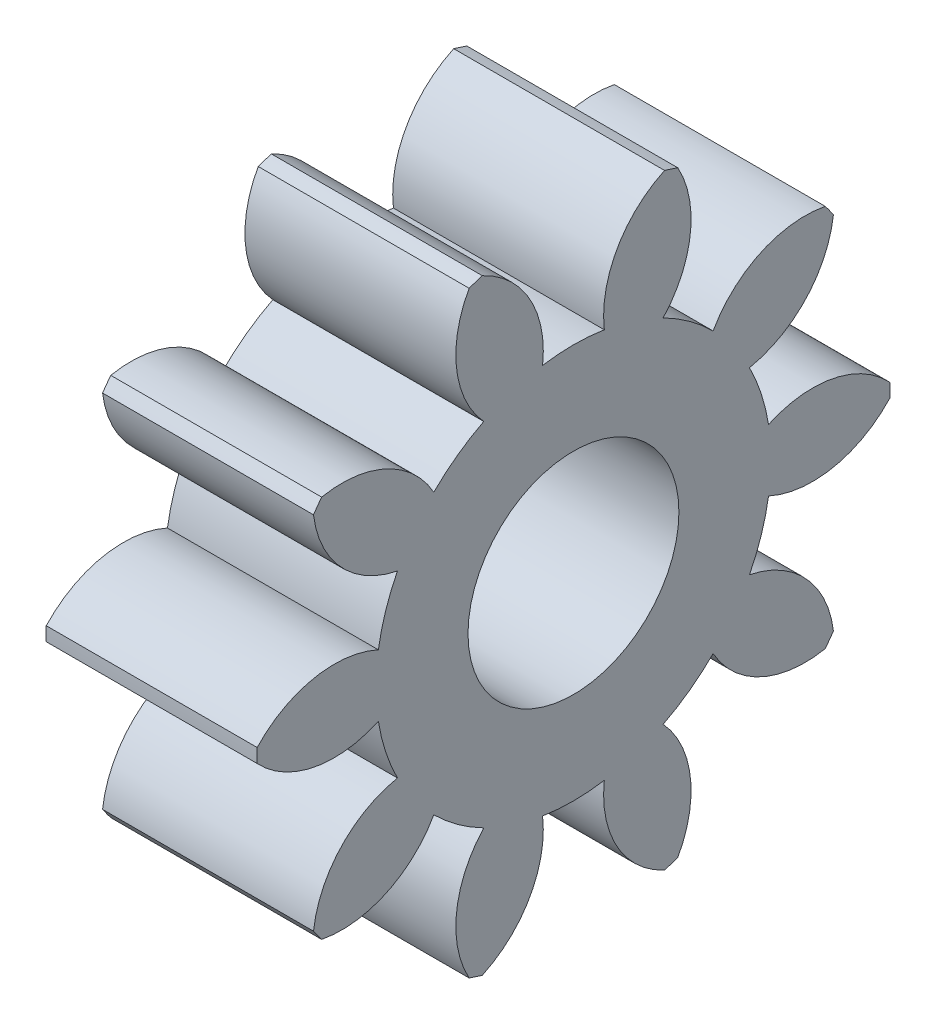
SolidWorks part; units mm, degrees
ref_plane "Plane1" through (0, 0, 0) normal (0, 0, 1) x (1, 0, 0)
ref_plane "Plane2" through (0, 0, 0) normal (0, 1, 0) x (1, 0, 0)
ref_plane "Plane3" through (0, 0, 0) normal (1, 0, 0) x (0, 0, -1)
sketch "HoldingSke" plane through (0, 0, 0) normal (0, 1, 0) x (1, 0, 0)
  line L0 (0, 0) -> (3.9392, -0.6946)
  line L1 (-15, 0) -> (100, 0) construction
  line L2 (0, 0) -> (-2.1039, 2.3779)
  line L3 (0, 0) -> (-11.863, 4.5341)
  line L4 (0, 0) -> (8.5048, 1.4996)
  line L5 (0, 0) -> (-46.8476, -17.4728)
  line L6 (0, 0) -> (-0.829, -0.5593)
  line L7 (-2.1039, 2.3779) -> (8.6586, 51.2059)
  line L8 (-76.2, 54.61) -> (-76.1, 54.61)
  line L9 (-71.009, 38.7566) -> (-53.1078, 45.2721)
  line L10 (-76.2, 71.12) -> (104.1128, 71.12)
  line L11 (0, 0) -> (-1, 0)
  line L12 (-76.2, 101.6) -> (-76.192, 101.6)
  line L13 (24.9733, 27.94) -> (52.9518, 28.4284)
  line L14 (24.9733, 27.94) -> (24.9743, 27.94)
  line L15 (24.9733, 27.94) -> (100.4006, 29.5858)
  line L16 (-63.627, -0.25) -> (-12.827, -0.25)
  circle A0 centre (0, 0) radius 0.5
  circle A1 centre (0, 0) radius 0.9365
  circle A2 centre (0, 0) radius 37.5
  circle A3 centre (0, 0) radius 0.5
  dimension "Num_teeth" = 10
  dimension "Pitch_radius" = 180.3128
  dimension "Width" = 1
  dimension "Thickness" = 1
sketch "BasProSke" plane through (0, 0, 0) normal (0, 1, 0) x (1, 0, 0)
  line L0 (-10, 0) -> (60, 0) construction
  line L1 (0, 0) -> (0, 1.5)
  line L2 (0, 0) -> (1, 0)
  line L3 (1, 0) -> (1, 1.5)
  line L4 (1, 1.5) -> (0, 1.5)
  dimension "Thickness" = 1
revolve "Base-Revolve" add sketch "BasProSke" angle 360 about L0
sketch "TooCutSke" plane through (0, 0, 0) normal (1, 0, 0) x (0, 0, -1)
  line L1 (0, 0) -> (0, 107) construction
  line L2 (0, 0) -> (-0.2095, 1.2323) construction
  line L3 (0, 0) -> (-0.7644, 2.3524) construction
  line L4 (-0.2095, 1.2323) -> (-0.3822, 1.1762) construction
  arc A0 (0.1463, 0.925) -> (-0.1463, 0.925) centre (0, 0) ccw
  arc A1 (0.4686, 1.4516) -> (-0.4686, 1.4516) centre (0, 0) ccw
  circle A2 centre (0, 0) radius 1.25 construction
  circle A3 centre (0, 0) radius 1.1746 construction
  arc A4 (-0.1463, 0.925) -> (-0.4686, 1.4516) centre (-0.6429, 0.983) ccw
  arc A5 (0.4686, 1.4516) -> (0.1463, 0.925) centre (0.6429, 0.983) ccw
extrude "ToothCut" cut sketch "TooCutSke" along normal through all
fillet "Breaks" [suppressed] radius 0.005 tangent propagation no
fillet "RootFillets" [suppressed] radius 0.0635
pattern_circular "TeethCuts" count 10 every 36 about axis through (-10, 0, 0) along (1, 0, 0) of "ToothCut", "RootFillets", "Breaks"
sketch "HubNeaOneSke" plane through (0, 0, 0) normal (-1, 0, 0) x (0, 0, 1)
  circle A0 centre (0, 0) radius 0.9365
extrude "HubNearOne" [suppressed] add sketch "HubNeaOneSke" along normal blind 49.0001
sketch "HubNeaBotSke" plane through (0, 0, 0) normal (-1, 0, 0) x (0, 0, 1)
  circle A0 centre (0, 0) radius 0.9365
extrude "HubNearBoth" [suppressed] add sketch "HubNeaBotSke" along normal blind 24.5
ref_plane "FarPln" through (1, 0, 0) normal (1, 0, 0) x (0, 0, -1)
sketch "HubFarSke" plane through (1, 0, 0) normal (1, 0, 0) x (0, 0, -1)
  circle A0 centre (0, 0) radius 0.9365
extrude "HubFar" [suppressed] add sketch "HubFarSke" along normal blind 24.5
sketch "BorSke" plane through (0, 0, 0) normal (1, 0, 0) x (0, 0, -1)
  circle A0 centre (0, 0) radius 0.5
  dimension "Diameter" = 1
extrude "Bore" cut sketch "BorSke" along normal mid plane 100.0001
sketch "KeySke" plane through (0, 0, 0) normal (1, 0, 0) x (0, 0, -1)
  line L0 (-0.05, 0) -> (-0.05, 0.6)
  line L1 (-0.05, 0.6) -> (0.05, 0.6)
  line L2 (0.05, 0.6) -> (0.05, 0)
  line L3 (0, 0) -> (0, 34) construction
  line L4 (-0.05, 0) -> (0.05, 0)
extrude "Keyway" [suppressed] cut sketch "KeySke" along normal mid plane 100.0001
pattern_circular "Keyway2" [suppressed] count 2 every 90 about axis through (-10, 0, 0) along (1, 0, 0) reverse direction yes
equation "' \"Module@HoldingSke\" = 6.35"
equation "' \"Num_teeth@HoldingSke\" = 12"
equation "' \"Ap@HoldingSke\" =  20"
equation "' \"Ap@HoldingSke\" = 20"
equation "' \"Width@HoldingSke\" = 0.5 * 25.4"
equation "' \"Hub_dia@HoldingSke\"= 1 * 25.4"
equation "' \"Hub_dia@HoldingSke\" = 1 * 25.4"
equation "' \"Overall_len@HoldingSke\" = 1.0 * 25.4"
equation "' \"Bore@HoldingSke\" = 0.75 * 25.4"
equation "' \"T_dim@HoldingSke\" = 0.1 * 25.4"
equation "' \"Width@KeySke\" = 0.25 * 25.4"
equation "' \"Show_teeth@HoldingSke\" = 13"
equation "' \"Backlash@HoldingSke\" = 0.009 * 25.4"
equation "' \"Addendum_fac@HoldingSke\" = 1.0"
equation "' \"Dedendum_fac@HoldingSke\" = 1.25"
equation "' \"Dedendum_add@HoldingSke\" = 0.00005 * 25.4"
equation "' \"Clearance_fac@HoldingSke\" = 0.25"
equation "\"Pitch@HoldingSke\" = 1 / \"Module@HoldingSke\""
equation "\"Overcut_dia@TooCutSke\" = (\"Num_teeth@HoldingSke\" + 2 * \"Addendum_fac@HoldingSke\") / \"Pitch@HoldingSke\" + 0.002 * 25.4"
equation "\"Pitch_dia@TooCutSke\" = \"Num_teeth@HoldingSke\" / \"Pitch@HoldingSke\""
equation "\"Base_dia@TooCutSke\" = \"Num_teeth@HoldingSke\" / \"Pitch@HoldingSke\" * cos((\"Ap@HoldingSke\"  * 3.14159265 / 180))"
equation "\"Root_dia@TooCutSke\" = (\"Num_teeth@HoldingSke\" + 2) / \"Pitch@HoldingSke\" - 2 * (\"Addendum_fac@HoldingSke\" + \"Dedendum_fac@HoldingSke\") / \"Pitch@HoldingSke\" - \"Dedendum_add@HoldingSke\" * 2"
equation "\"Half_ang@TooCutSke\" = 180 / \"Num_teeth@HoldingSke\""
equation "\"Half_CT@TooCutSke\" = \"Num_teeth@HoldingSke\" / \"Pitch@HoldingSke\" * sin((3.14159265 / 2 / \"Num_teeth@HoldingSke\")) / 2 - 7 * \"Backlash@HoldingSke\" / 4"
equation "\"Flank_rad@TooCutSke\" = \"Num_teeth@HoldingSke\" / \"Pitch@HoldingSke\" / 5"
equation "\"Radius@RootFillets\" = \"Clearance_fac@HoldingSke\" / \"Pitch@HoldingSke\" + \"Dedendum_add@HoldingSke\""
equation "\"Break_rad@Breaks\" = 0.02 / \"Pitch@HoldingSke\""
equation "\"Thickness@HoldingSke\" = \"Width@HoldingSke\""
equation "\"OAL@HoldingSke\" = \"Thickness@HoldingSke\""
equation "\"MHD@HoldingSke\" = (\"Num_teeth@HoldingSke\" + 2) / \"Pitch@HoldingSke\" - 2 * (\"Addendum_fac@HoldingSke\" + \"Dedendum_fac@HoldingSke\")  / \"Pitch@HoldingSke\" - \"Dedendum_add@HoldingSke\" * 2"
equation "\"MBD@HoldingSke\" = (\"Num_teeth@HoldingSke\" + 2) / \"Pitch@HoldingSke\" - 2 * (\"Addendum_fac@HoldingSke\" + \"Dedendum_fac@HoldingSke\")  / \"Pitch@HoldingSke\" - \"Dedendum_add@HoldingSke\" * 2 - 0.002 * 25.4"
equation "\"MHD@HoldingSke\" = ((sgn( \"MHD@HoldingSke\" - \"Hub_dia@HoldingSke\" )-1)*( \"MHD@HoldingSke\" - \"Hub_dia@HoldingSke\" ))/-2+ \"Hub_dia@HoldingSke\""
equation "\"MBD@HoldingSke\" = ((sgn( \"MBD@HoldingSke\" - \"Bore@HoldingSke\" )-1)*( \"MBD@HoldingSke\" - \"Bore@HoldingSke\" ))/-2+ \"Bore@HoldingSke\""
equation "\"OAL@HoldingSke\" = ((sgn( \"OAL@HoldingSke\" - \"Overall_len@HoldingSke\" )+1)*( \"OAL@HoldingSke\" - \"Overall_len@HoldingSke\" ))/2 + \"Overall_len@HoldingSke\" + 0.000002 * 25.4"
equation "\"Num_teeth@TeethCuts\" = int( \"Show_teeth@HoldingSke\" ) + 1"
equation "\"Num_teeth@TeethCuts\" = ((sgn( \"Num_teeth@TeethCuts\" - \"Num_teeth@HoldingSke\" )-1)*( \"Num_teeth@TeethCuts\" - \"Num_teeth@HoldingSke\" ))/-2+ \"Num_teeth@HoldingSke\""
equation "\"Num_teeth@TeethCuts\" = ((sgn( \"Num_teeth@TeethCuts\" - 2.0)+1)*( \"Num_teeth@TeethCuts\" - 2.0))/2 +2.0"
equation "\"Angle@TeethCuts\" = 360.0 / \"Num_teeth@HoldingSke\""
equation "\"Diameter@BasProSke\" = (\"Num_teeth@HoldingSke\" + 2 * \"Addendum_fac@HoldingSke\") / \"Pitch@HoldingSke\""
equation "\"Thickness@BasProSke\"  = \"Thickness@HoldingSke\""
equation "' \"Fillet_rad@BasProSke\" =  \"Thickness@HoldingSke\" * 0.05"
equation "' \"Fillet_rad@BasProSke\" = \"Thickness@HoldingSke\" * 0.05"
equation "\"MHD@HoldingSke\" = ((sgn( \"MHD@HoldingSke\" - \"Root_dia@TooCutSke\" )-1)*( \"MHD@HoldingSke\" - \"Root_dia@TooCutSke\" ))/-2+ \"Root_dia@TooCutSke\""
equation "\"Diameter@HubNeaOneSke\" = \"MHD@HoldingSke\""
equation "\"Length@HubNearOne\" = \"OAL@HoldingSke\" - \"Thickness@BasProSke\""
equation "\"Diameter@HubNeaBotSke\" = \"MHD@HoldingSke\""
equation "\"Length@HubNearBoth\" = ( \"OAL@HoldingSke\" - \"Thickness@BasProSke\" ) / 2.0"
equation "\"Thickness@FarPln\" = \"Thickness@BasProSke\""
equation "\"Diameter@HubFarSke\" = \"MHD@HoldingSke\""
equation "\"Length@HubFar\" = ( \"OAL@HoldingSke\" - \"Thickness@BasProSke\" ) / 2.0"
equation "\"Diameter@BorSke\" = \"MBD@HoldingSke\""
equation "\"D1@Bore\" = \"OAL@HoldingSke\" * 2.0"
equation "\"D1@Keyway\" = \"OAL@HoldingSke\" * 2.0"
equation "\"Offset@KeySke\" = \"T_dim@HoldingSke\" + \"MBD@HoldingSke\" / 2.0"
